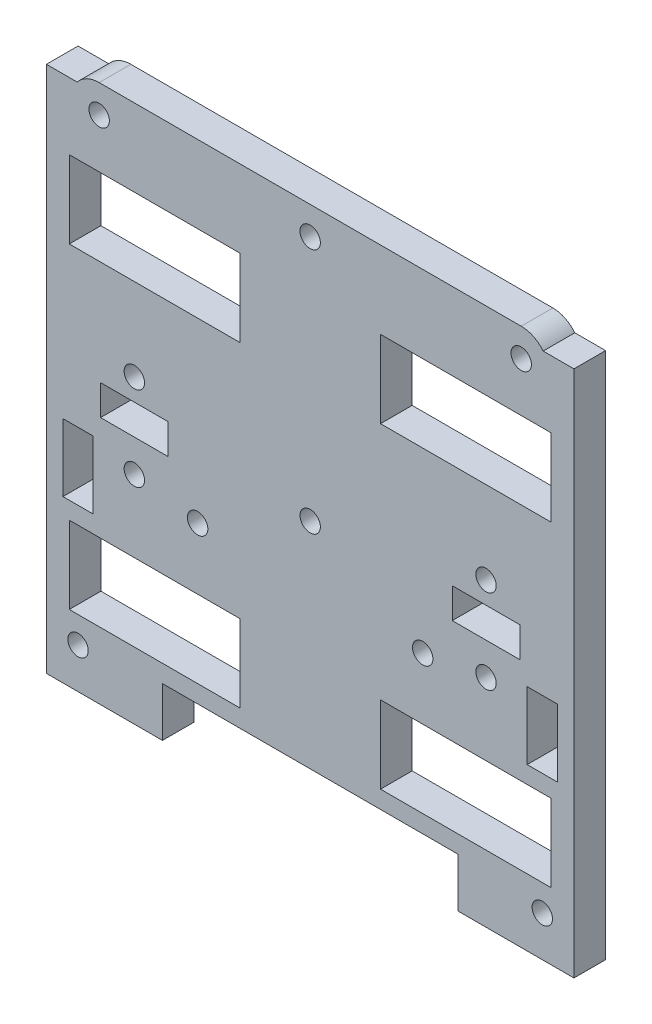
SolidWorks part; units mm, degrees
ref_plane "Front Plane" through (0, 0, 0) normal (0, 0, 1) x (1, 0, 0)
ref_plane "Top Plane" through (0, 0, 0) normal (0, 1, 0) x (1, 0, 0)
ref_plane "Right Plane" through (0, 0, 0) normal (1, 0, 0) x (0, 0, -1)
sketch "Sketch1" plane through (0, 0, 0) normal (0, 0, 1) x (1, 0, 0)
  line L0 (0, -37.5) -> (0, 37.5) construction
  line L1 (-47.5, -37.5) -> (47.5, -37.5)
  line L2 (-47.5, -37.5) -> (-47.5, 37.5)
  line L3 (-47.5, 37.5) -> (47.5, 37.5)
  line L4 (47.5, -37.5) -> (47.5, 37.5)
  line L5 (-47.5, -37.5) -> (47.5, 37.5) construction
  line L6 (-47.5, 37.5) -> (47.5, -37.5) construction
  line L7 (-47.5, 0) -> (47.5, 0) construction
  line L8 (-47.5, 22.5) -> (47.5, 22.5) construction
  line L9 (34.25, 17) -> (10, 28) construction
  line L10 (-34.25, 28) -> (-10, 28)
  line L11 (-34.25, 28) -> (-34.25, 17)
  line L12 (-34.25, 17) -> (-10, 17)
  line L13 (-10, 28) -> (-10, 17)
  line L14 (-34.25, 28) -> (-10, 17) construction
  line L15 (-34.25, 17) -> (-10, 28) construction
  line L16 (34.25, 28) -> (10, 17) construction
  line L17 (10, 28) -> (10, 17)
  line L18 (34.25, 17) -> (10, 17)
  line L19 (34.25, 28) -> (34.25, 17)
  line L20 (34.25, 28) -> (10, 28)
  line L21 (34.25, -28) -> (10, -17) construction
  line L22 (-34.25, -17) -> (-10, -28) construction
  line L23 (-34.25, -28) -> (-10, -17) construction
  line L24 (34.25, -17) -> (10, -28) construction
  line L25 (34.25, -28) -> (10, -28)
  line L26 (34.25, -28) -> (34.25, -17)
  line L27 (34.25, -17) -> (10, -17)
  line L28 (10, -28) -> (10, -17)
  line L29 (-10, -28) -> (-10, -17)
  line L30 (-34.25, -17) -> (-10, -17)
  line L31 (-34.25, -28) -> (-34.25, -17)
  line L32 (-34.25, -28) -> (-10, -28)
  point P0 (0, 0)
  point P12 (-22.125, 22.5)
  point P21 (22.125, 22.5)
  point P30 (22.125, -22.5)
  point P31 (-22.125, -22.5)
  dimension "D1" = 95
  dimension "D2" = 75
  dimension "D3" = 22.5
  dimension "D4" = 24.25
  dimension "D5" = 11
  dimension "D6" = 10
extrude "Boss-Extrude1" add sketch "Sketch1" along normal blind 4.5
sketch "Sketch8" plane through (0, 0, 4.5) normal (0, 0, 1) x (1, 0, 0)
  line L0 (-47.5, 37.5) -> (-47.5, -37.5) construction
  line L1 (47.5, -37.5) -> (47.5, 37.5) construction
  circle A0 centre (-47.5, 29.5) radius 8
  circle A1 centre (47.5, 29.5) radius 8
  dimension "D1" = 16
extrude "Boss-Extrude2" [suppressed] add sketch "Sketch8" against normal through all
sketch "Sketch2" plane through (0, 0, 4.5) normal (0, 0, 1) x (1, 0, 0)
  line L0 (0, -37.5) -> (0, 37.5) construction
  line L1 (-47.5, -37.5) -> (47.5, -37.5) construction
  line L2 (47.5, 37.5) -> (-47.5, 37.5) construction
  line L3 (-47.5, 0) -> (47.5, 0) construction
  line L4 (-47.5, 37.5) -> (-47.5, -37.5) construction
  line L5 (47.5, -37.5) -> (47.5, 37.5) construction
  line L6 (-40, 0) -> (40, 0) construction
  line L7 (-30, 35) -> (30, 35) construction
  circle A0 centre (-30, 35) radius 1.45
  circle A1 centre (30, 35) radius 1.45
  circle A2 centre (40, 0) radius 1.45
  circle A3 centre (-40, 0) radius 1.45
  circle A4 centre (0, 35) radius 1.45
  dimension "D1" = 2.9
  dimension "D7" = 2.9
  dimension "D8" = 2.9
  dimension "D9" = 2.9
  dimension "D2" = 30
  dimension "D3" = 35
  dimension "D4" = 80
  dimension "D5" = 40
  dimension "D6" = 0
extrude "screwHoles" cut sketch "Sketch2" against normal through all
sketch "Sketch3" plane through (0, 0, 4.5) normal (0, 0, 1) x (1, 0, 0)
  line L0 (-47.5, -20) -> (26.0486, -20) construction
  line L1 (-47.5, 37.5) -> (-47.5, -37.5) construction
  line L3 (0, 37.5) -> (0, -37.5) construction
  line L4 (47.5, 37.5) -> (-47.5, 37.5) construction
  line L5 (-47.5, -37.5) -> (47.5, -37.5) construction
  line L6 (18.95, -22.2) -> (9.05, -17.8) construction
  line L7 (-18.95, -17.8) -> (-9.05, -17.8)
  line L8 (-18.95, -17.8) -> (-18.95, -22.2)
  line L9 (-18.95, -22.2) -> (-9.05, -22.2)
  line L10 (-9.05, -17.8) -> (-9.05, -22.2)
  line L11 (-18.95, -17.8) -> (-9.05, -22.2) construction
  line L12 (-18.95, -22.2) -> (-9.05, -17.8) construction
  line L13 (18.95, -17.8) -> (9.05, -22.2) construction
  line L14 (9.05, -17.8) -> (9.05, -22.2)
  line L15 (18.95, -22.2) -> (9.05, -22.2)
  line L16 (18.95, -17.8) -> (18.95, -22.2)
  line L17 (18.95, -17.8) -> (9.05, -17.8)
  line L18 (-47.5, 37.5) -> (-47.5, -37.5) construction
  point P2 (-47.5, 0)
  point P12 (-14, -20)
  point P21 (14, -20)
  dimension "D1" = 9.9
  dimension "D2" = 4.4
  dimension "D3" = 14
  dimension "D4" = 20
extrude "BeltClamp" [suppressed] cut sketch "Sketch3" against normal through all
sketch "Sketch4" plane through (0, 0, 4.5) normal (0, 0, 1) x (1, 0, 0)
  line L0 (-47.5, 0) -> (47.5, 0) construction
  line L1 (-47.5, 37.5) -> (-47.5, -37.5) construction
  line L2 (47.5, -37.5) -> (47.5, 37.5) construction
  line L3 (0, 0) -> (0, 33.55) construction
  line L4 (-29.8, 2.15) -> (-20.2, 2.15)
  line L5 (-29.8, 2.15) -> (-29.8, -2.15)
  line L6 (-29.8, -2.15) -> (-20.2, -2.15)
  line L7 (-20.2, 2.15) -> (-20.2, -2.15)
  line L8 (-29.8, 2.15) -> (-20.2, -2.15) construction
  line L9 (-29.8, -2.15) -> (-20.2, 2.15) construction
  line L10 (29.8, -2.15) -> (20.2, 2.15) construction
  line L11 (29.8, 2.15) -> (20.2, -2.15) construction
  line L12 (20.2, 2.15) -> (20.2, -2.15)
  line L13 (29.8, -2.15) -> (20.2, -2.15)
  line L14 (29.8, 2.15) -> (29.8, -2.15)
  line L15 (29.8, 2.15) -> (20.2, 2.15)
  line L16 (-29.8, -2.15) -> (-20.2, 2.15) construction
  circle A0 centre (-40, 0) radius 1.45 construction
  circle A1 centre (0, 35) radius 1.45 construction
  circle A2 centre (0, 0) radius 1.45
  point P6 (-25, 0)
  point P22 (25, 0)
  dimension "D5" = 2.9
  dimension "D3" = 0
  dimension "D1" = 9.6
  dimension "D2" = 4.3
  dimension "D4" = 25
extrude "Cut-Extrude3" cut sketch "Sketch4" against normal through all
sketch "Sketch5" plane through (0, 0, 4.5) normal (0, 0, 1) x (1, 0, 0)
  line L0 (-47.5, -9.75) -> (47.5, -9.75) construction
  line L1 (-47.5, 37.5) -> (-47.5, -37.5) construction
  line L2 (47.5, -37.5) -> (47.5, 37.5) construction
  line L4 (0, -37.5) -> (0, 37.5) construction
  line L5 (-47.5, -37.5) -> (47.5, -37.5) construction
  line L6 (47.5, 37.5) -> (-47.5, 37.5) construction
  line L7 (-30.85, -14.55) -> (-35.15, -4.95) construction
  line L8 (30.85, -4.95) -> (35.15, -4.95)
  line L9 (30.85, -4.95) -> (30.85, -14.55)
  line L10 (30.85, -14.55) -> (35.15, -14.55)
  line L11 (35.15, -4.95) -> (35.15, -14.55)
  line L12 (30.85, -4.95) -> (35.15, -14.55) construction
  line L13 (30.85, -14.55) -> (35.15, -4.95) construction
  line L14 (-30.85, -4.95) -> (-35.15, -14.55) construction
  line L15 (-35.15, -4.95) -> (-35.15, -14.55)
  line L16 (-30.85, -14.55) -> (-35.15, -14.55)
  line L17 (-30.85, -4.95) -> (-30.85, -14.55)
  line L18 (-30.85, -4.95) -> (-35.15, -4.95)
  line L19 (33, -9.75) -> (33, -37.5) construction
  line L20 (-33, -9.75) -> (-33, -37.5) construction
  line L21 (-33, -31.75) -> (33, -31.75) construction
  circle A0 centre (33, -31.75) radius 1.45
  circle A1 centre (-33, -31.75) radius 1.45
  point P15 (33, -9.75)
  point P24 (-33, -9.75)
  dimension "D5" = 2.9
  dimension "D2" = 9.6
  dimension "D3" = 4.3
  dimension "D4" = 33
  dimension "D6" = 22
  dimension "D1" = 9.75
extrude "Cut-Extrude4" cut sketch "Sketch5" against normal through all
sketch "Sketch9" plane through (0, 0, 4.5) normal (0, 0, 1) x (1, 0, 0)
  line L0 (47.5, 37.5) -> (-47.5, 37.5) construction
  line L1 (0, 37.5) -> (0, -37.5) construction
  line L2 (-47.5, -37.5) -> (47.5, -37.5) construction
  line L3 (50.5, 35) -> (45.5, 35) construction
  line L4 (-50.5, 35) -> (-45.5, 35) construction
  circle A0 centre (-30, 35) radius 4
  circle A1 centre (-30, 35) radius 1.45
  circle A2 centre (-30, 35) radius 1.45 construction
  circle A3 centre (30, 35) radius 1.45
  circle A4 centre (30, 35) radius 4
  point P17 (0, -37.5)
  dimension "D1" = 8
extrude "Boss-Extrude3" add sketch "Sketch9" against normal through all
sketch "Sketch10" plane through (0, 0, 4.5) normal (0, 0, 1) x (1, 0, 0)
  line L0 (-60, 37.5) -> (-37.5, 37.5)
  line L1 (-37.5, 37.5) -> (-37.5, -37.5)
  line L2 (-47.5, -37.5) -> (47.5, -37.5) construction
  line L3 (-37.5, -37.5) -> (-60, -37.5)
  line L4 (-60, -37.5) -> (-60, 37.5)
  line L5 (0, 37.5) -> (0, -37.5) construction
  line L6 (26.8775, 37.5) -> (-26.8775, 37.5) construction
  line L7 (60, -37.5) -> (60, 37.5)
  line L8 (37.5, -37.5) -> (60, -37.5)
  line L9 (37.5, 37.5) -> (37.5, -37.5)
  line L10 (60, 37.5) -> (37.5, 37.5)
  line L11 (-60, -37.5) -> (-60, 37.5)
  line L12 (-33.1225, 37.5) -> (-47.5, 37.5) construction
  line M3 (47.5, -37.5) -> (47.5, 37.5)
  line M7 (-47.5, 37.5) -> (-47.5, -37.5)
  line M8 (-47.5, -37.5) -> (47.5, -37.5)
  dimension "D3" = 0
  dimension "D1" = 75
  dimension "D2" = 60
extrude "Cut-Extrude5" cut sketch "Sketch10" against normal through all contours L1 L0 M7 M8 | L10 L9 M3 M8 region at (42.5, 0, 4.5) region at (-42.5, 0, 4.5)
sketch "Sketch11" plane through (0, 0, 4.5) normal (0, 0, 1) x (1, 0, 0)
  line L0 (-30, 39) -> (30, 39)
  line L1 (30, 39) -> (26.8775, 37.5)
  line L2 (26.8775, 37.5) -> (-26.8775, 37.5)
  line L3 (-26.8775, 37.5) -> (-30, 39)
  arc A0 (-26.8775, 37.5) -> (-33.1225, 37.5) centre (-30, 35) ccw construction
  arc A1 (33.1225, 37.5) -> (26.8775, 37.5) centre (30, 35) ccw construction
extrude "Boss-Extrude4" add sketch "Sketch11" against normal through all
sketch "Sketch12" plane through (0, 0, 4.5) normal (0, 0, 1) x (1, 0, 0)
  line L0 (-37.5, -8.25) -> (37.5, -8.25) construction
  line L1 (-37.5, 37.5) -> (-37.5, -37.5) construction
  line L2 (37.5, 37.5) -> (37.5, -37.5) construction
  line L3 (0, 0) -> (0, -37.5) construction
  line L4 (-37.5, -37.5) -> (37.5, -37.5) construction
  circle A0 centre (-16, -8.25) radius 1.45
  circle A1 centre (16, -8.25) radius 1.45
  dimension "D2" = 2.9
  dimension "D1" = 16
  dimension "D3" = 8.25
extrude "FanBraceScrews" cut sketch "Sketch12" against normal through all
sketch "Sketch13" plane through (0, 0, 4.5) normal (0, 0, 1) x (1, 0, 0)
  line L0 (-37.5, -37.5) -> (37.5, -37.5) construction
  line L1 (-21, -44.5) -> (21, -44.5)
  line L2 (-21, -44.5) -> (-21, -30.5)
  line L3 (-21, -30.5) -> (21, -30.5)
  line L4 (21, -44.5) -> (21, -30.5)
  line L5 (-21, -44.5) -> (21, -30.5) construction
  line L6 (-21, -30.5) -> (21, -44.5) construction
  point P0 (0, -37.5)
  dimension "D1" = 42
  dimension "D2" = 7
extrude "Cut-Extrude7" cut sketch "Sketch13" against normal through all
sketch "Sketch14" plane through (0, 0, 4.5) normal (0, 0, 1) x (1, 0, 0)
  line L0 (16, -9.7) -> (16, 3.75) construction
  line L1 (0, 0) -> (0, -40.3958) construction
  line L2 (-16, -9.7) -> (-16, 3.75) construction
  circle A0 centre (16, -8.25) radius 1.45 construction
  circle A1 centre (16, 3.75) radius 1.45
  circle A2 centre (-16, 3.75) radius 1.45
  dimension "D2" = 2.9
  dimension "D1" = 12
extrude "Cut-Extrude8" [suppressed] cut sketch "Sketch14" against normal through all
sketch "Sketch15" plane through (0, 0, 4.5) normal (0, 0, 1) x (1, 0, 0)
  line L0 (-25, 5.25) -> (-25, -6.75) construction
  line L2 (0, 0) -> (0, -11.0705) construction
  line L3 (16, -8.3509) -> (25, -6.75) construction
  line L4 (25, 5.25) -> (25, -6.75) construction
  circle A0 centre (-25, 5.25) radius 1.45
  circle A1 centre (-25, -6.75) radius 1.45
  circle A2 centre (25, -6.75) radius 1.45
  circle A3 centre (25, 5.25) radius 1.45
  circle A5 centre (-16, -8.25) radius 1.45 construction
  dimension "D1" = 12
  dimension "D3" = 2.9
  dimension "D4" = 2.9
  dimension "D2" = 25
  dimension "D5" = 1.5
extrude "BeltClipScrews" cut sketch "Sketch15" against normal through all
sketch "Sketch16" [suppressed] plane through (0, 0, 4.5) normal (0, 0, 1) x (1, 0, 0)
  line L0 (0, 0) -> (0, -11.3016) construction
  line L1 (-30.1, 2.35) -> (-19.9, 2.35)
  line L2 (-30.1, 2.35) -> (-30.1, -2.35)
  line L3 (-30.1, -2.35) -> (-19.9, -2.35)
  line L4 (-19.9, 2.35) -> (-19.9, -2.35)
  line L5 (-35.35, -4.65) -> (-30.65, -4.65)
  line L6 (-35.35, -4.65) -> (-35.35, -14.85)
  line L7 (-35.35, -14.85) -> (-30.65, -14.85)
  line L8 (-30.65, -4.65) -> (-30.65, -14.85)
  line L9 (30.65, -4.65) -> (30.65, -14.85)
  line L10 (35.35, -14.85) -> (30.65, -14.85)
  line L11 (35.35, -4.65) -> (35.35, -14.85)
  line L12 (35.35, -4.65) -> (30.65, -4.65)
  line L13 (19.9, 2.35) -> (19.9, -2.35)
  line L14 (30.1, -2.35) -> (19.9, -2.35)
  line L15 (30.1, 2.35) -> (30.1, -2.35)
  line L16 (30.1, 2.35) -> (19.9, 2.35)
  line L17 (-30.65, -4.65) -> (-30.65, -14.85)
extrude "Boss-Extrude5" [suppressed] add sketch "Sketch16" against normal through all contours L8 L5 L6 L7 | L4 L1 L2 L3 | L15 L16 L13 L14 | L11 L12 L9 L10
equation "\"X-ROD-SPACING\"=45"
equation "\"Y-ROD-SPACING\"=75"
equation "\"Z-ROD-SPACING\"=17.5"
equation "\"Y-BED-OFFSET\"=2"
equation "\"Y-BED-ROD-INSET\"=3.5"
equation "\"Y-BED-SCREW-SPACING\"=209"
equation "\"Y-BED-SCREW-CUTOUT-SLOT-HEIGHT\"=2"
equation "\"T-SLOT-NUT-FILLET-RADIUS\"=0.5"
equation "\"T-SLOT-SCREW-SHAFT-RADIUS\"=1.55"
equation "\"T-SLOT-SCREW-SHAFT-CUTOUT-LENGTH\"=11"
equation "\"T-SLOT-NUT-DEPTH\"=3.5"
equation "\"T-SLOT-NUT-WIDTH\"=2.85"
equation "\"T-SLOT-NUT-END-DISTANCE\"=8"
equation "\"ACRYLIC-THICKNESS\"=10"
equation "\"ACRYLIC-THICKNESS2\"=4.5"
equation "\"ACRYLIC-TAB-CUTOUT-SIZE\"=\"ACRYLIC-THICKNESS\"+\"ACRYLIC-TAB-TOLERANCE\"*2"
equation "\"ACRYLIC-TAB-WIDTH\"=\"ACRYLIC-THICKNESS\""
equation "\"ACRYLIC-M3-HOLE\"=2.9"
equation "\"SMOOTHROD-CAP-SCREW-DISTANCE\"=20"
equation "\"FRAME-WIDTH-INNER\"=370"
equation "\"NEMA17-HOLE-SPACING\"=31"
equation "\"NEMA17-CENTRAL-CUTOUT\"=22.5"
equation "\"Z-BRACKET-REACH\"=55"
equation "\"Z-ROD-INSET\"=13.5"
equation "\"TOP-BRACKET-SPACING\"=40"
equation "\"SMOOTHROD-X-LENGTH\"=350"
equation "\"SMOOTHROD-Y-LENGTH\"=350"
equation "\"SMOOTHROD-Z-LENGTH\"=350"
equation "\"SMOOTHROD-TIGHTENING-HEADROOM\"=.25"
equation "\"LEADSCREW-Z-LENGTH\"=300"
equation "\"SCREW-LENGTH-FRAME\"=\"ACRYLIC-THICKNESS\" + 10"
equation "\"SCREW-LENGTH-MOTOR\"=\"ACRYLIC-THICKNESS\" + 5"
equation "\"SCREW-HEAD-RADIUS\"=6"
equation "\"PRINTED-X-SMOOTHROD-DIAMETER\"=9.0"
equation "\"PRINTED-X-SMOOTHROD-CUTOUT\"=10"
equation "\"PRINTED-X-BASE-HEIGHT\"=10"
equation "\"PRINTED-LM8UU-CUTOUT-SIZE\"=15.5"
equation "\"PRINTED-LM8UU-CUTOUT-LENGTH\"=24.5"
equation "\"PRINTED-X-IDLER-HEIGHT\"=16"
equation "\"PSU-MOUNTING-WIDTH\"=95"
equation "\"PSU-MOUNTING-HEIGHT\"=177"
equation "\"Y-BELT-TO-ROD-DISTANCE\"=20"
equation "\"SPOOL-HOLDER-ROD-SPACING\"=150"
equation "\"D3@Sketch1\"=\"X-ROD-SPACING\"/2"
equation "\"D4@Sketch1\"=\"ACRYLIC-X-CARRIAGE-LM8UU-CUTOUT-WIDTH\""
equation "\"D1@Boss-Extrude1\"=\"ACRYLIC-THICKNESS2\""
equation "\"D1@Sketch2\"=\"ACRYLIC-M3-HOLE\""
equation "\"D1@Sketch3\"=\"ACRYLIC-TAB-CUTOUT-SIZE\""
equation "\"D2@Sketch3\"=\"ACRYLIC-THICKNESS2\"+\"ACRYLIC-TAB-TOLERANCE\"*2"
equation "\"ACRYLIC-X-CARRIAGE-WIDTH\"=55"
equation "\"ACRYLIC-X-CARRIAGE-HEIGHT\"=75"
equation "\"D2@Sketch1\"=\"ACRYLIC-X-CARRIAGE-HEIGHT\""
equation "\"ACRYLIC-X-CARRIAGE-CENTER-TAB-SPACING\"=14"
equation "\"D3@Sketch3\"=\"ACRYLIC-X-CARRIAGE-CENTER-TAB-SPACING\""
equation "\"SCREW-LENGTH-EXTRUDER\"=28"
equation "\"ACRYLIC-X-CARRIAGE-SCREW-SPACING-X\"=15"
equation "\"ACRYLIC-X-CARRIAGE-SCREW-SPACING-Y\"=33"
equation "\"D1@Sketch4\"=\"ACRYLIC-TAB-WIDTH\"-\"KERF\"*4"
equation "\"D2@Sketch4\"=\"ACRYLIC-THICKNESS2\"-\"KERF\"*2"
equation "\"D2@Sketch5\"=\"ACRYLIC-TAB-WIDTH\"-\"KERF\"*4"
equation "\"D3@Sketch5\"=\"ACRYLIC-THICKNESS2\"-\"KERF\"*2"
equation "\"ACRYLIC-X-CARRIAGE-EXTRUDER-SHELF-DEPTH\"=\"ACRYLIC-X-CARRIAGE-EXTRUDER-OFFSET\" + 28"
equation "\"ACRYLIC-X-CARRIAGE-EXTRUDER-BRACE-SPACING\"=23"
equation "\"D4@Sketch5\"=\"ACRYLIC-X-CARRIAGE-DUAL-MOUNT-BRACE-WIDTH\""
equation "\"D1@Sketch5\"=\"ACRYLIC-THICKNESS2\"/2 + 7.5"
equation "\"D4@Sketch2\"=\"ACRYLIC-X-CARRIAGE-DUAL-MOUNT-SCREW-WIDTH\"*2"
equation "\"D5@Sketch2\"=\"ACRYLIC-X-CARRIAGE-DUAL-MOUNT-SCREW-WIDTH\""
equation "\"D7@Sketch2\"=\"ACRYLIC-M3-HOLE\""
equation "\"D8@Sketch2\"=\"ACRYLIC-M3-HOLE\""
equation "\"ACRYLIC-X-CARRIAGE-LM8UU-CUTOUT-WIDTH\"=24.25"
equation "\"ACRYLIC-TAB-TOLERANCE\"=-.05"
equation "\"ACRYLIC-X-CARRIAGE-EXTRUDER-OFFSET\"=26"
equation "\"ACRYLIC-X-CARRIAGE-EXTRUDER-ANGLE\"=90"
equation "\"ACRYLIC-X-CARRIAGE-EXTRUDER-BRACE-TAB-OFFSET\"=20"
equation "\"ACRYLIC-X-CARRIAGE-EXTRUDER-BRACE-HEIGHT\"=35"
equation "\"ACRYLIC-X-CARRIAGE-EXTRUDER-BRACE-SCREW-SPACING\"=22"
equation "\"D5@Sketch5\"=\"ACRYLIC-M3-HOLE\""
equation "\"ACRYLIC-X-CARRIAGE-DUAL-WIDTH-MULTIPLIER\"=1.65"
equation "\"ACRYLIC-X-CARRIAGE-DUAL-HOTEND-SPACING\"=42"
equation "\"ACRYLIC-X-CARRIAGE-DUAL-WIDTH\"=75"
equation "\"ACRYLIC-X-CARRIAGE-DUAL-HOTEND-SEPARATION\"=36"
equation "\"ACRYLIC-X-CARRIAGE-DUAL-MOUNT-PLATE-DEPTH\"=75"
equation "\"ACRYLIC-X-CARRIAGE-DUAL-MOUNT-BRACE-WIDTH\"=33"
equation "\"ACRYLIC-X-CARRIAGE-DUAL-MOUNT-SCREW-WIDTH\"=40"
equation "\"D9@Sketch2\"=\"ACRYLIC-M3-HOLE\""
equation "\"ACRYLIC-X-CARRIAGE-LM8UU-CUTOUT-HEIGHT\"=11.0"
equation "\"D5@Sketch1\"=\"ACRYLIC-X-CARRIAGE-LM8UU-CUTOUT-HEIGHT\""
equation "\"D1@Sketch10\"=\"ACRYLIC-X-CARRIAGE-DUAL-WIDTH\""
equation "\"D5@Sketch4\"=\"ACRYLIC-M3-HOLE\""
equation "\"D2@Sketch12\"=\"ACRYLIC-M3-HOLE\""
equation "\"D3@Sketch12\"=\"ACRYLIC-THICKNESS2\"/2 + 6"
equation "\"D2@Sketch14\"=\"ACRYLIC-M3-HOLE\""
equation "\"D3@Sketch15\"=\"ACRYLIC-M3-HOLE\""
equation "\"D4@Sketch15\"=\"ACRYLIC-M3-HOLE\""
equation "\"KERF\"=0.1"
equation "\"ACRYLIC-THICKNESS-TAB-CUTOUT-WIDTH\"=\"ACRYLIC-THICKNESS\"-\"KERF\"*2"
equation "\"ACRYLIC-THICKNESS-TAB-CUTOUT-HEIGHT\"=\"ACRYLIC-TAB-WIDTH\"-\"KERF\"*4"
equation "\"ACRYLIC-THICKNESS2-TAB-CUTOUT-WIDTH\"=\"ACRYLIC-THICKNESS2\"-\"KERF\"*2"
equation "\"ACRYLIC-THICKNESS2-TAB-CUTOUT-HEIGHT\"=\"ACRYLIC-TAB-WIDTH\"-\"KERF\"*4"
equation "\"PRINTED-M3-HOLE\"=3.5"
equation "\"PRINTED-M3-NUT-AF\"=6.25"
equation "\"ACRYLIC-X-CARRIAGE-DUAL-FAN-OFFSET\"=52"
equation "\"ACRYLIC-X-CARRIAGE-DUAL-FAN-HEIGHT\"=20"
equation "\"BLOWER-FAN-WIDTH\"=15"
